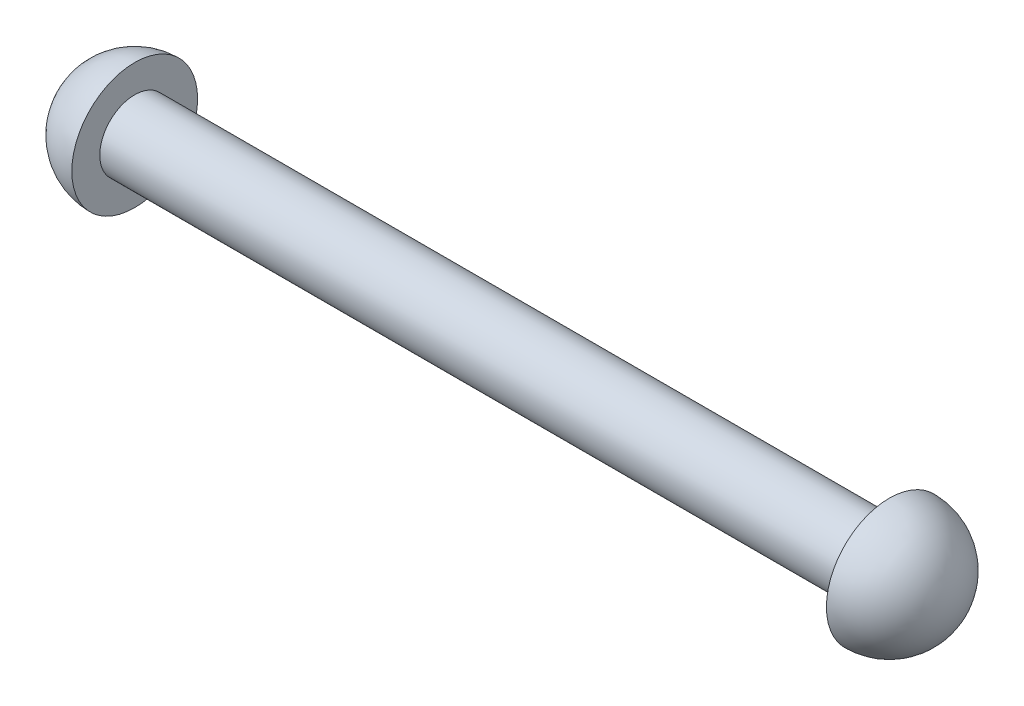
SolidWorks part; units mm, degrees
material "AISI 1020"
ref_plane "Front Plane" through (0, 0, 0) normal (0, 0, 1) x (1, 0, 0)
ref_plane "Top Plane" through (0, 0, 0) normal (0, 1, 0) x (1, 0, 0)
ref_plane "Right Plane" through (0, 0, 0) normal (1, 0, 0) x (0, 0, -1)
sketch "Sketch1" plane through (0, 0, 0) normal (0, 0, 1) x (1, 0, 0)
  line L0 (0, 8.89) -> (0, -2.54)
  line L1 (0, 0) -> (68.58, 0)
  line L2 (0, 0) -> (0, 6.35)
  line L3 (0, 6.35) -> (68.58, 6.35)
  line L4 (68.58, 0) -> (68.58, 6.35)
  line L5 (68.58, 8.89) -> (68.58, -2.54)
  line L6 (-5.715, 3.175) -> (74.295, 3.175) construction
  arc A0 (0, 8.89) -> (0, -2.54) centre (0, 3.175) ccw
  arc A1 (68.58, -2.54) -> (68.58, 8.89) centre (68.58, 3.175) ccw
  dimension "D3" = 5.715
  dimension "D1" = 68.58
  dimension "D2" = 6.35
revolve "Revolve1" add sketch "Sketch1" angle 360 about L6 region at (-2.4255, 5.6005, 0) region at (34.29, 4.7625, 0) region at (71.0055, 5.6005, 0)
